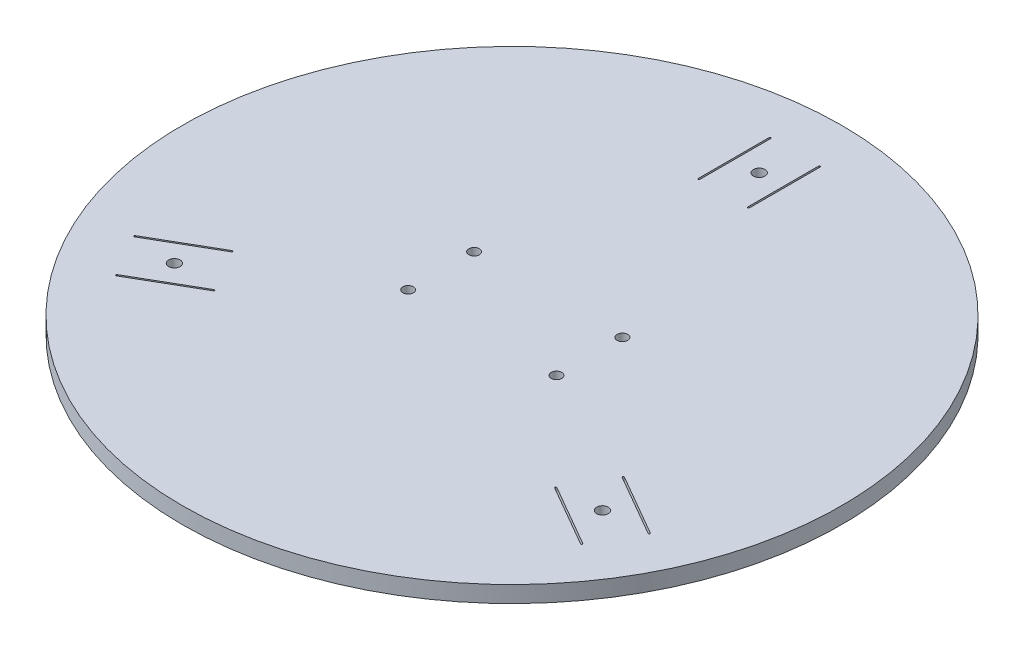
SolidWorks part; units mm, degrees
material "Acrylic (Medium-high impact)"
ref_plane "Front Plane" through (0, 0, 0) normal (0, 0, 1) x (1, 0, 0)
ref_plane "Top Plane" through (0, 0, 0) normal (0, 1, 0) x (1, 0, 0)
ref_plane "Right Plane" through (0, 0, 0) normal (1, 0, 0) x (0, 0, -1)
sketch "Sketch2" plane through (0, 0, 0) normal (0, 1, 0) x (1, 0, 0)
  circle A0 centre (0, 0) radius 100
  dimension "D1" = 200
extrude "Boss-Extrude1" add sketch "Sketch2" along normal blind 5
sketch "Sketch3" plane through (0, 5, 0) normal (0, 1, 0) x (1, 0, 0)
  line L0 (0, 0) -> (0, 100) construction
  line L1 (-7.5, 75) -> (7.5, 75) construction
  line L3 (-7.75, 64) -> (-7.25, 64)
  line L4 (-7.75, 64) -> (-7.75, 86)
  line L5 (-7.75, 86) -> (-7.25, 86)
  line L6 (-7.25, 64) -> (-7.25, 86)
  line L7 (-7.75, 64) -> (-7.25, 86) construction
  line L8 (-7.75, 86) -> (-7.25, 64) construction
  line L9 (7.25, 64) -> (7.75, 64)
  line L10 (7.25, 64) -> (7.25, 86)
  line L11 (7.25, 86) -> (7.75, 86)
  line L12 (7.75, 64) -> (7.75, 86)
  line L13 (7.25, 64) -> (7.75, 86) construction
  line L14 (7.25, 86) -> (7.75, 64) construction
  line L30 (59.3006, -25.2883) -> (78.3532, -36.2883)
  line L31 (59.3006, -25.2883) -> (59.0506, -25.7213)
  line L32 (59.0506, -25.7213) -> (78.1032, -36.7213)
  line L33 (78.3532, -36.2883) -> (78.1032, -36.7213)
  line L34 (51.8006, -38.2787) -> (70.8532, -49.2787)
  line L35 (51.8006, -38.2787) -> (51.5506, -38.7117)
  line L36 (51.5506, -38.7117) -> (70.6032, -49.7117)
  line L37 (70.8532, -49.2787) -> (70.6032, -49.7117)
  line L38 (-51.5506, -38.7117) -> (-70.6032, -49.7117)
  line L39 (-51.5506, -38.7117) -> (-51.8006, -38.2787)
  line L40 (-51.8006, -38.2787) -> (-70.8532, -49.2787)
  line L41 (-70.6032, -49.7117) -> (-70.8532, -49.2787)
  line L42 (-59.0506, -25.7213) -> (-78.1032, -36.7213)
  line L43 (-59.0506, -25.7213) -> (-59.3006, -25.2883)
  line L44 (-59.3006, -25.2883) -> (-78.3532, -36.2883)
  line L45 (-78.1032, -36.7213) -> (-78.3532, -36.2883)
  circle A0 centre (0, 0) radius 100 construction
  circle A1 centre (0, 75) radius 1.75
  circle A2 centre (64.9519, -37.5) radius 1.75
  circle A3 centre (-64.9519, -37.5) radius 1.75
  point P8 (0, 75)
  point P34 (0, 0)
  point P36 (0, 0)
  point P42 (0, 0)
  dimension "D6" = 3.5
  dimension "D1" = 15
  dimension "D2" = 22
  dimension "D3" = 0.5
  dimension "D4" = 75
  dimension "D7" = 3
  dimension "D5" = 3
extrude "Cut-Extrude1" cut sketch "Sketch3" against normal through all
sketch "Sketch6" plane through (0, 0, 0) normal (0, -1, 0) x (-1, 0, 0)
  line L0 (0, 0) -> (0, 50000) construction
  line L1 (0, 0) -> (50000, 0) construction
  point P0 (-22.5, 11)
  point P2 (22.5, 11)
  point P4 (22.5, -9)
  point P6 (-22.5, -9)
  dimension "D1" = 45
  dimension "D2" = 11
  dimension "D3" = 20
hole_wizard "Ø3.2 (3.2) Diameter Hole1" positions "Sketch6" profile "Sketch5" hole size "Ø3.2" standard "ANSI Metric" end condition through all
sketch "Sketch5" plane through (22.5, 0, -11) normal (1, 0, 0) x (0, 0, -1)
  line L0 (0, 0) -> (0, 5)
  line L1 (0, 5) -> (1.6, 5)
  line L2 (1.6, 5) -> (1.6, 0.025)
  line L3 (1.6, 0.025) -> (1.625, 0)
  line L5 (1.625, 0) -> (0, 0)
  line L6 (-1.6, 0.025) -> (-1.625, 0) construction
  line L11 (0, -6.35) -> (0, 107.95) construction
  dimension "Thru Hole Dia." = 3.2
  dimension "Thru Hole Depth" = 5
  dimension "Near C'Sink Dia." = 3.25
  dimension "Near C'Sink Angle" = 90
fillet "Fillet1" radius 0.2 24 edges at (59.0506, 2.5, 25.7213) (59.3006, 2.5, 25.2883) (78.3532, 2.5, 36.2883) (78.1032, 2.5, 36.7213) (-59.3006, 2.5, 25.2883) (-59.0506, 2.5, 25.7213) (-78.1032, 2.5, 36.7213) (-78.3532, 2.5, 36.2883) (-51.8006, 2.5, 38.2787) (-51.5506, 2.5, 38.7117) (-70.6032, 2.5, 49.7117) (-70.8532, 2.5, 49.2787) (51.5506, 2.5, 38.7117) (51.8006, 2.5, 38.2787) (70.8532, 2.5, 49.2787) (70.6032, 2.5, 49.7117) (7.25, 2.5, -64) (7.25, 2.5, -86) (7.75, 2.5, -86) (7.75, 2.5, -64) (-7.75, 2.5, -64) (-7.25, 2.5, -86) (-7.25, 2.5, -64) (-7.75, 2.5, -86)
equation "\"Leg_Spacing\"=40"
equation "\"Leaf_Spring_Slot_Width\"=5"
equation "\"Leaf_Spring_Thickness\"=0.2"
equation "\"Inner_Radius\"=75"
equation "\"Camera\"=120"
